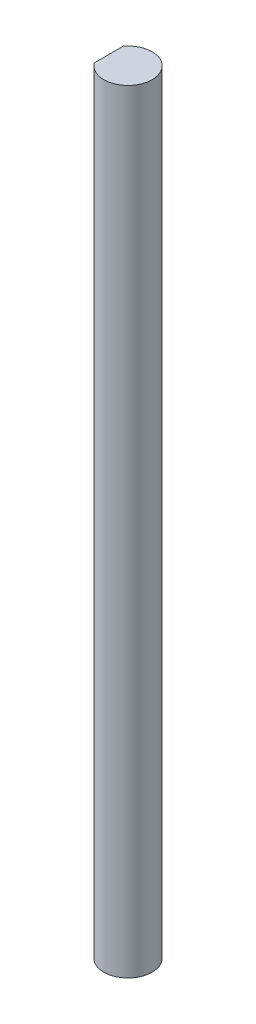
SolidWorks part; units mm, degrees
ref_plane "Front Plane" through (0, 0, 0) normal (0, 0, 1) x (1, 0, 0)
ref_plane "Top Plane" through (0, 0, 0) normal (0, 1, 0) x (1, 0, 0)
ref_plane "Right Plane" through (0, 0, 0) normal (1, 0, 0) x (0, 0, -1)
sketch "Sketch1" plane through (0, 0, 0) normal (0, 1, 0) x (1, 0, 0)
  line L0 (-2.54, -1.905) -> (-2.54, 1.905)
  line L1 (0, -3.175) -> (0, 3.175) construction
  line L2 (-2.54, 0) -> (3.175, 0) construction
  arc A0 (-2.54, -1.905) -> (-2.54, 1.905) centre (0, 0) ccw
  dimension "D1" = 6.35
  dimension "D2" = 5.715
extrude "Boss-Extrude1" add sketch "Sketch1" along normal mid plane 101.6
